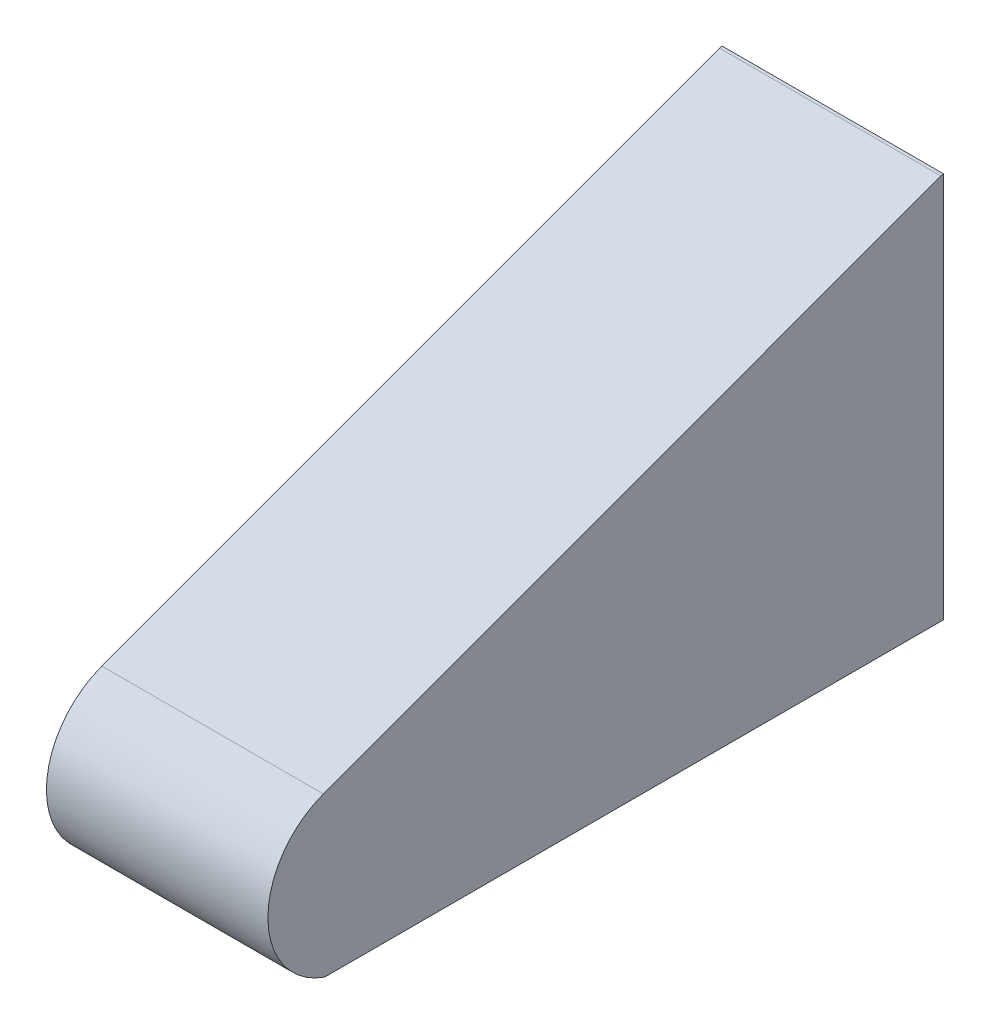
SolidWorks part; units mm, degrees
material "Thornel Mat VMA Foam Core (2)"
ref_plane "Front Plane" through (0, 0, 0) normal (0, 0, 1) x (1, 0, 0)
ref_plane "Top Plane" through (0, 0, 0) normal (0, 1, 0) x (1, 0, 0)
ref_plane "Right Plane" through (0, 0, 0) normal (1, 0, 0) x (0, 0, -1)
sketch "Sketch1" plane through (0, 0, 0) normal (1, 0, 0) x (0, 0, -1)
  line L0 (0, -114.3) -> (0, 114.3) construction
  line L1 (0, 75.1586) -> (0, -75.1586) construction
  line L2 (75.1586, 0) -> (-75.1586, 0) construction
  line L3 (0, 0) -> (-381, 0) construction
  line L4 (0, -114.3) -> (-381, -114.3)
  line L5 (-381, -114.3) -> (-381, -25.4) construction
  line L6 (-381, -25.4) -> (0, 114.3)
  line L11 (0, 114.3) -> (0, 119.126)
  line L13 (0, -119.126) -> (-381.8355, -119.126)
  line L14 (-382.6614, -20.869) -> (-1.6614, 118.831)
  line L15 (0, -119.126) -> (0, -114.3)
  line L16 (-1.6614, 118.831) -> (0, 119.126)
  arc A0 (-381, -25.4) -> (-381, -114.3) centre (-364.7017, -69.85) ccw
  arc A1 (-382.6614, -20.869) -> (-381.8355, -119.126) centre (-364.7017, -69.85) ccw
  dimension "D1" = 114.3
  dimension "D2" = 114.3
  dimension "D3" = 381
  dimension "D4" = 88.9
  dimension "D6" = 4.826
  dimension "D5" = 4.826
extrude "Boss-Extrude1" add sketch "Sketch1" along normal blind 63.5 and the other way blind 63.5
sketch "Sketch2" plane through (63.5, 0, 0) normal (1, 0, 0) x (0, 0, -1)
  line L9 (-381.8355, -119.126) -> (0, -119.126) construction
  line L10 (-1.6614, 118.831) -> (-382.6614, -20.869) construction
  line L11 (-381.8355, -119.126) -> (0, -119.126)
  line L12 (-1.6614, 118.831) -> (-382.6614, -20.869)
  line L13 (0, 119.126) -> (-1.6614, 118.831) construction
  line L14 (0, 119.126) -> (-1.6614, 118.831)
  line L15 (0, 119.126) -> (0, -119.126)
  arc A1 (-382.6614, -20.869) -> (-381.8355, -119.126) centre (-364.7017, -69.85) ccw construction
  arc A2 (-382.6614, -20.869) -> (-381.8355, -119.126) centre (-364.7017, -69.85) ccw
extrude "Boss-Extrude2" add sketch "Sketch2" along normal blind 4.826
mirror "Mirror1" about plane through (0, 0, 0) normal (1, 0, 0) of "Boss-Extrude2"
